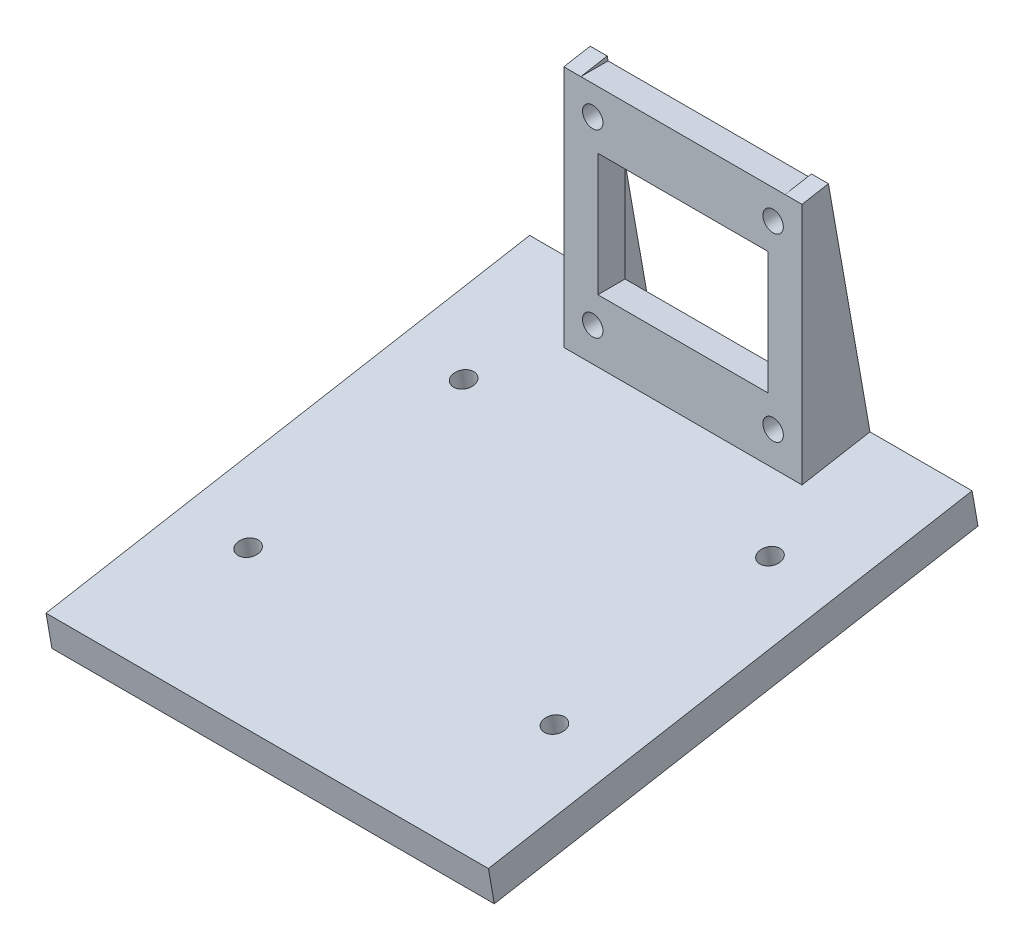
SolidWorks part; units mm, degrees
ref_plane "前视基准面" through (0, 0, 0) normal (0, 0, 1) x (1, 0, 0)
ref_plane "上视基准面" through (0, 0, 0) normal (0, 1, 0) x (1, 0, 0)
ref_plane "右视基准面" through (0, 0, 0) normal (1, 0, 0) x (0, 0, -1)
sketch "草图1" plane through (0, 0, 0) normal (0, 0, 1) x (1, 0, 0)
  line L0 (17.5, 0) -> (17.5, -35) construction
  line L1 (0, 0) -> (35, 0)
  line L2 (0, 0) -> (0, -35)
  line L3 (0, -35) -> (35, -35)
  line L4 (35, 0) -> (35, -35)
  line L5 (4.25, -17.5) -> (17.5, -17.5) construction
  line L6 (30.75, -30.75) -> (4.25, -30.75) construction
  line L7 (30.75, -30.75) -> (30.75, -4.25) construction
  line L8 (30.75, -4.25) -> (4.25, -4.25) construction
  line L9 (4.25, -30.75) -> (4.25, -4.25) construction
  line L10 (30.75, -30.75) -> (4.25, -4.25) construction
  line L11 (30.75, -4.25) -> (4.25, -30.75) construction
  line L13 (5, -26.5) -> (30, -26.5)
  line L14 (5, -26.5) -> (5, -8.5)
  line L15 (5, -8.5) -> (30, -8.5)
  line L16 (30, -26.5) -> (30, -8.5)
  line L17 (5, -26.5) -> (30, -8.5) construction
  line L18 (5, -8.5) -> (30, -26.5) construction
  circle A0 centre (4.25, -4.25) radius 1.5
  circle A1 centre (30.75, -30.75) radius 1.5
  circle A2 centre (30.75, -4.25) radius 1.5
  circle A3 centre (4.25, -30.75) radius 1.5
  point P7 (17.5, -17.5)
  dimension "D5" = 3
  dimension "D1" = 35
  dimension "D2" = 35
  dimension "D3" = 25
  dimension "D4" = 26.5
  dimension "D6" = 18
  dimension "D7" = 8.5
extrude "凸台-拉伸1" add sketch "草图1" along normal blind 4
sketch "草图2" plane through (0, 0, 0) normal (-1, 0, 0) x (0, 0, 1)
  line L0 (0, -35) -> (-5.9854, -33.9446) construction
  line L1 (-5.9854, -33.9446) -> (0, 0) construction
  line L2 (0, 0) -> (0, -35) construction
  dimension "D1" = 80
ref_plane "基准面4" through (0, -33.9446, -5.9854) normal (0, -0.9848, -0.1736) x (-1, 0, 0)
sketch "草图3" plane through (0, -33.9446, -5.9854) normal (0, -0.9848, -0.1736) x (-1, 0, 0)
  line L0 (0, -6.0777) -> (-35, -6.0777) construction
  line L1 (-35, 0) -> (-32.5, 0)
  line L3 (-35, -6.0777) -> (-32.5, -6.0777)
  line L5 (-35, 0) -> (-35, -6.0777)
  line L7 (0, 0) -> (0, -6.0777)
  line L12 (-32.5, 0) -> (-32.5, -6.0777)
  line L14 (0, 0) -> (-2.5, 0)
  line L16 (0, -6.0777) -> (-2.5, -6.0777)
  line L17 (-2.5, 0) -> (-2.5, -6.0777)
  dimension "D2" = 2.5
  dimension "D3" = 2.5
extrude "凸台-拉伸2" add sketch "草图3" against normal through all
sketch "草图4" plane through (35, 0, 0) normal (1, 0, 0) x (0, 0, -1)
  line L3 (-4, 0) -> (-6.106, -0.3713)
  line L4 (-4, -12.3149) -> (-4, 0)
  line L5 (-6.106, -0.3713) -> (-4, -12.3149)
  line L6 (-4, 0) -> (-6.106, -0.3713)
  line L7 (-4, -12.3149) -> (-4, 0)
  line L8 (-6.106, -0.3713) -> (-4, -12.3149)
  dimension "D1" = 0
extrude "切除-拉伸1" cut sketch "草图4" against normal up to surface (35 mm away) up to face at (0, -19.3245, 1.3735)
sketch "草图5" plane through (0, -33.9446, -5.9854) normal (0, -0.9848, -0.1736) x (-1, 0, 0)
  line L0 (-17.5, -6.0777) -> (-17.5, -36.0777) construction
  line L1 (-2.5, -6.0777) -> (-32.5, -6.0777) construction
  line L2 (15, -72.1554) -> (15, 0)
  line L3 (15, -72.1554) -> (-50, -72.1554)
  line L4 (15, 0) -> (-50, 0)
  line L5 (-50, -72.1554) -> (-50, 0)
  line L6 (15, -72.1554) -> (-50, 0) construction
  line L7 (15, 0) -> (-50, -72.1554) construction
  line L8 (-32.5, 0) -> (-35, 0) construction
  dimension "D1" = 65
  dimension "D2" = 30
extrude "凸台-拉伸3" add sketch "草图5" along normal blind 5 separate body
sketch "草图6" plane through (0, 0, 0) normal (-1, 0, 0) x (0, 0, 1)
  line L0 (4, -35) -> (4, -35.7053)
  line L1 (65.0738, -46.4743) -> (-5.9854, -33.9446) construction
  line L2 (4, -35.7053) -> (0, -35)
  line L3 (0, -35) -> (4, -35)
extrude "凸台-拉伸4" add sketch "草图6" against normal up to surface (35 mm away) up to face at (35, -20.6521, 0.4271)
sketch "草图7" plane through (0, -33.9446, -5.9854) normal (0, 0.9848, 0.1736) x (1, 0, 0)
  line L0 (-15, -20) -> (-5, -20) construction
  line L1 (-15, -72.1554) -> (-15, 0) construction
  line L2 (-15, 0) -> (0, 0) construction
  line L3 (17.5, -72.1554) -> (17.5, -52.86) construction
  line L4 (50, -72.1554) -> (-15, -72.1554) construction
  line L5 (-15, -52.1554) -> (-5, -52.1554) construction
  circle A0 centre (-5, -20) radius 1.5
  circle A1 centre (-5, -52.1554) radius 1.5
  circle A2 centre (40, -52.1554) radius 1.5
  circle A3 centre (40, -20) radius 1.5
  dimension "D5" = 3
  dimension "D6" = 3
  dimension "D1" = 20
  dimension "D2" = 10
  dimension "D3" = 20
  dimension "D4" = 10
extrude "切除-拉伸2" cut sketch "草图7" against normal up to surface (5 mm away) up to face at (17.5, -45.1335, 28.676)
